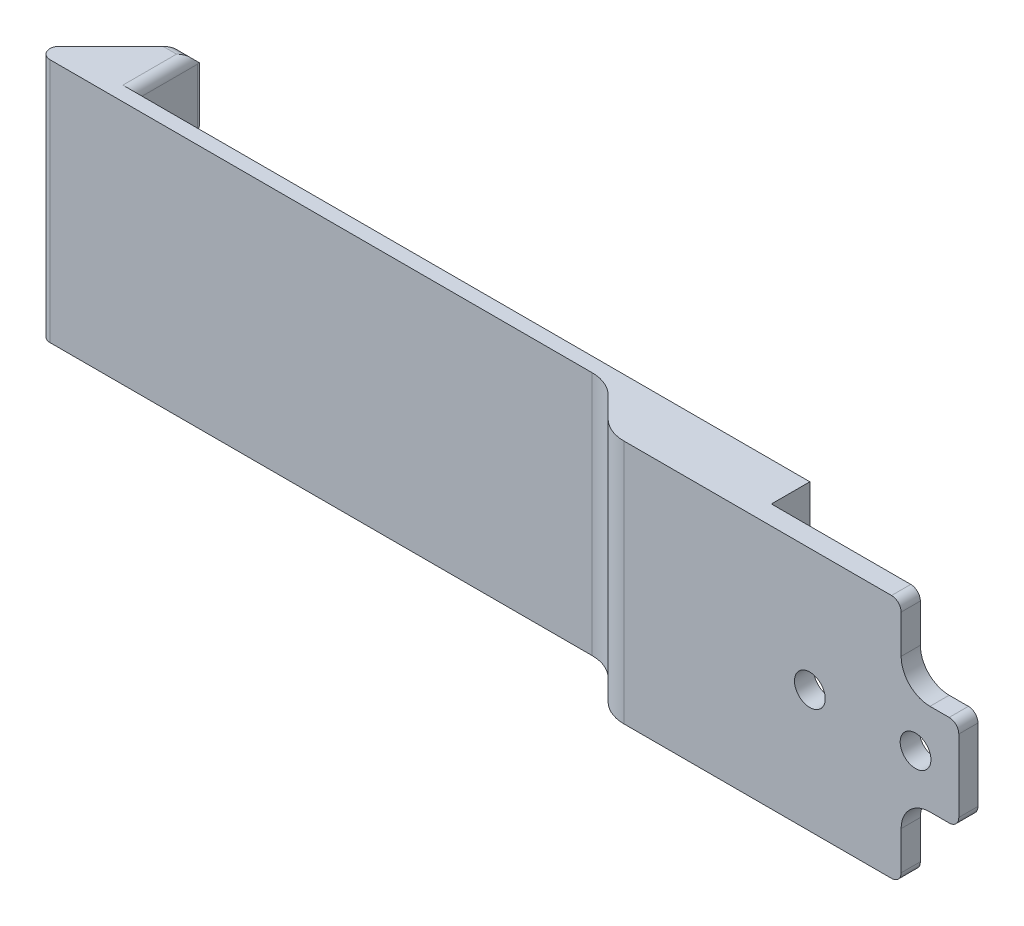
SolidWorks part; units mm, degrees
ref_plane "Спереди" through (0, 0, 0) normal (0, 0, 1) x (1, 0, 0)
ref_plane "Сверху" through (0, 0, 0) normal (0, 1, 0) x (1, 0, 0)
ref_plane "Справа" through (0, 0, 0) normal (1, 0, 0) x (0, 0, -1)
sketch "Эскиз1" plane through (0, 0, 0) normal (0, 0, 1) x (1, 0, 0)
  line L0 (-21.5, -12.75) -> (-21.5, 12.75) construction
  line L1 (0, 0) -> (50000, 0) construction
  line L2 (0, 4.7601) -> (0, -4.7601)
  line L3 (0, 4.7601) -> (0, -4.7601) construction
  line L4 (0, -4.7601) -> (-3, -4.7601)
  line L5 (-6, -7.7601) -> (-6, -12.75)
  line L6 (-6, -12.75) -> (-6, -9.9563) construction
  line L7 (-6, -12.75) -> (-36.5, -12.75)
  line L8 (-36.5, -12.75) -> (-36.5, 12.75)
  line L9 (-6, 12.75) -> (-36.5, 12.75)
  line L10 (-6, 7.7601) -> (-6, 12.75)
  line L11 (0, 4.7601) -> (-3, 4.7601)
  circle A0 centre (-15.5, 0) radius 1.6
  circle A1 centre (-4.5, 0) radius 1.6
  arc A2 (-3, -4.7601) -> (-6, -7.7601) centre (-3, -7.7601) ccw
  arc A3 (-3, 4.7601) -> (-6, 7.7601) centre (-3, 7.7601) cw
  dimension "D1" = 3.2
  dimension "D2" = 15
extrude "Бобышка-Вытянуть1" add sketch "Эскиз1" along normal blind 2
sketch "Эскиз2" plane through (0, -12.75, 0) normal (0, -1, 0) x (1, 0, 0)
  line L1 (-101.5, -2.5) -> (-92, -12)
  line L2 (-92, -12) -> (-92, -4)
  line L3 (-36.5, 0) -> (-6, 0) construction
  line L4 (-21.5, 0) -> (-21.5, -4)
  line L5 (-21.5, -4) -> (-92, -4)
  line L6 (-21.5, 0) -> (-36.5, 0)
  line L7 (-36.5, 0) -> (-36.5, 2)
  line L8 (-41, -2.5) -> (-101.5, -2.5)
  line L9 (-36.5, 2) -> (-41, -2.5)
  line L10 (-21.5, -68.5) -> (-21.5, -4) construction
  point P13 (-101.881, -2.5)
  point P18 (-92, 2.5777)
  point P19 (-92, -3.3679)
  point P20 (0, 0)
  point P21 (0, 0)
  point P23 (0, 0)
  point P24 (-44.6211, -1.6211)
  dimension "D1" = 45
  dimension "D2" = 8
  dimension "D3" = 45
  dimension "D4" = 70.5
  dimension "D5" = 1.5
extrude "Бобышка-Вытянуть2" add sketch "Эскиз2" against normal up to surface (25.5 mm away) up to face at (-21.25, 12.75, 1)
sketch "Эскиз3" plane through (-92, 0, 0) normal (1, 0, 0) x (0, 0, -1)
  line L0 (0, 0) -> (-50000, 0) construction
  line L2 (5.5, -5) -> (10, -5)
  line L3 (5.5, -5) -> (5.5, 5)
  line L4 (5.5, 5) -> (10, 5)
  line L5 (12, -5) -> (12, 5)
  line L6 (5.5, -5) -> (12, 5) construction
  line L7 (5.5, 5) -> (12, -5) construction
  line L8 (2, -12.75) -> (2, 12.75) construction
  line L9 (12, 12.75) -> (12, -12.75) construction
  line L10 (10, 5) -> (12, 7)
  line L11 (12, 12.75) -> (12, -12.75) construction
  line L12 (12, 7) -> (12, 5)
  line L13 (12, -7) -> (12, -5)
  line L14 (10, -5) -> (12, -7)
  line L15 (12, 12.75) -> (10, 12.75)
  line L16 (4, 12.75) -> (12, 12.75) construction
  line L17 (10, 12.75) -> (12, 10.75)
  line L18 (12, 10.75) -> (12, 12.75)
  line L19 (12, -10.75) -> (12, -12.75)
  line L20 (12, -12.75) -> (10, -12.75)
  line L21 (10, -12.75) -> (12, -10.75)
  point P3 (8.75, 0)
  dimension "D1" = 10
  dimension "D2" = 3.5
  dimension "D3" = 2
  dimension "D4" = 45
extrude "Вырез-Вытянуть1" cut sketch "Эскиз3" against normal through all
fillet "Скругление3" radius 2 2 edges at (-95.25, -5, -5.5) (-95.25, 5, -5.5)
fillet "Скругление1" radius 1 16 edges at (-92, 12.75, -7) (-92, -12.75, -7) (-6, 12.75, 1) (-6, -12.75, 1) (0, -4.7601, 1) (0, 4.7601, 1) (-93, -5, -10) (-93, 5, -10) (-95.25, -5, -8.75) (-97.9142, -4.4142, -6.0858) (-95.25, 5, -8.75) (-97.9142, 4.4142, -6.0858) (-98.5, 0, -5.5) (-93, -12.75, -10) (-93, 12.75, -10) (-101.5, 0, -2.5)
fillet "Скругление2" radius 0.5 2 edges at (-92, -8.875, -12) (-92, 8.875, -12) tangent propagation no
fillet "Скругление4" radius 4 2 edges at (-36.5, 0, 2) (-41, 0, -2.5)
